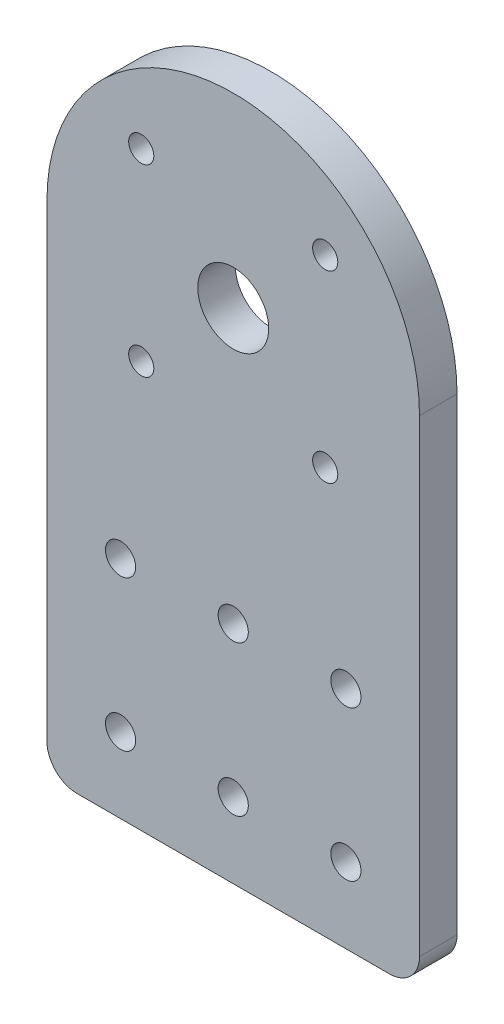
SolidWorks part; units mm, degrees
ref_plane "Front Plane" through (0, 0, 0) normal (0, 0, 1) x (1, 0, 0)
ref_plane "Top Plane" through (0, 0, 0) normal (0, 1, 0) x (1, 0, 0)
ref_plane "Right Plane" through (0, 0, 0) normal (1, 0, 0) x (0, 0, -1)
sketch "Sketch1" plane through (0, 0, 0) normal (0, 0, 1) x (1, 0, 0)
  line L0 (0, 0) -> (-11948.862, 0) construction
  line L1 (-0.5397, 50.8) -> (-11949.4017, 50.8) construction
  line L2 (31.5, 0) -> (31.5, 84.3)
  line L3 (-31.5, 84.3) -> (-31.5, 0)
  line L4 (-31.5, 0) -> (31.5, 0)
  line L5 (19.05, 12.7) -> (0, 12.7) construction
  line L6 (19.05, 12.7) -> (19.05, 38.1) construction
  line L7 (31.5, 12.7) -> (19.05, 12.7) construction
  line L8 (19.05, 12.7) -> (19.05, 0) construction
  line L9 (-31.5, 38.1) -> (-19.05, 38.1) construction
  line L10 (-19.05, 38.1) -> (-19.05, 50.8) construction
  circle A0 centre (0, 84.3) radius 33.5 construction
  circle A1 centre (0, 84.3) radius 22 construction
  circle A2 centre (-15.5563, 99.8563) radius 2.125
  circle A3 centre (15.5563, 99.8563) radius 2.125
  circle A4 centre (15.5563, 68.7437) radius 2.125
  circle A5 centre (-15.5563, 68.7437) radius 2.125
  arc A6 (31.5, 84.3) -> (-31.5, 84.3) centre (0, 84.3) ccw
  circle A7 centre (19.05, 12.7) radius 2.5527
  circle A8 centre (0, 12.7) radius 2.5527
  circle A9 centre (0, 38.1) radius 2.5527
  circle A10 centre (19.05, 38.1) radius 2.5527
  circle A11 centre (-19.05, 12.7) radius 2.5527
  circle A12 centre (-19.05, 38.1) radius 2.5527
  circle A13 centre (0, 84.3) radius 6
  point P19 (0, 84.3)
  dimension "D2" = 67
  dimension "D3" = 44
  dimension "D4" = 4.25
  dimension "D6" = 31.5
  dimension "D10" = 5.1054
  dimension "D11" = 25.4
  dimension "D13" = 12
  dimension "D1" = 50.8
  dimension "D9" = 90
  dimension "D12" = 19.05
  dimension "D7" = 3
  dimension "D8" = 2
  dimension "D5" = 4
extrude "Boss-Extrude1" add sketch "Sketch1" along normal blind 6.35
fillet "Fillet1" radius 5.08 2 edges at (-31.5, 0, 3.175) (31.5, 0, 3.175)
